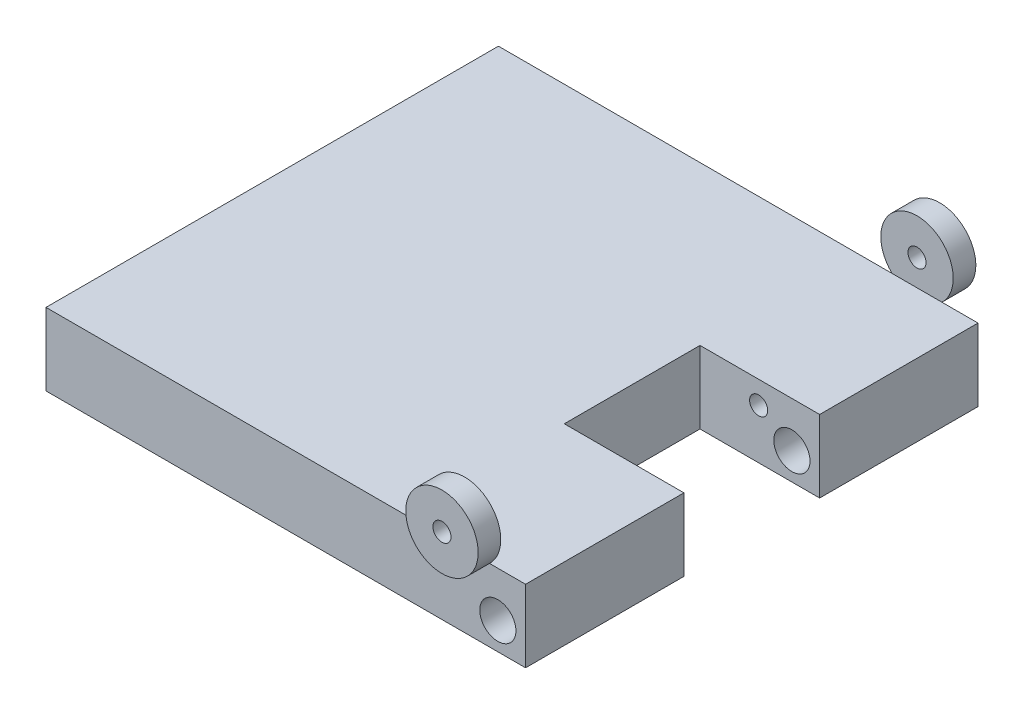
SolidWorks part; units mm, degrees
material "ABS"
ref_plane "Front Plane" through (0, 0, 0) normal (0, 0, 1) x (1, 0, 0)
ref_plane "Top Plane" through (0, 0, 0) normal (0, 1, 0) x (1, 0, 0)
ref_plane "Right Plane" through (0, 0, 0) normal (1, 0, 0) x (0, 0, -1)
sketch "Sketch1" plane through (0, 0, 0) normal (0, 0, 1) x (1, 0, 0)
  line L4 (0.9398, -1.27) -> (-66.3702, -1.27)
  line L5 (-66.3702, -1.27) -> (-66.3702, 8.89)
  line L6 (-66.3702, 8.89) -> (0.9398, 8.89)
  line L7 (0.9398, 8.89) -> (0.9398, -1.27)
  circle A6 centre (-2.9549, 2.54) radius 2.54
  point P3 (0, 0)
  dimension "D1" = 67.31
  dimension "D2" = 10.16
  dimension "D3" = 5.08
extrude "Boss-Extrude2" add sketch "Sketch1" along normal blind 63.5
sketch "Sketch2" plane through (0.9398, 0, 0) normal (1, 0, 0) x (0, 0, -1)
  line L0 (-31.75, 8.89) -> (-22.225, 8.89)
  line L1 (-63.5, 8.89) -> (0, 8.89) construction
  line L2 (-31.75, 8.89) -> (-41.275, 8.89)
  line L4 (-41.275, 8.89) -> (-41.275, -1.27)
  line L5 (-63.5, -1.27) -> (0, -1.27) construction
  line L6 (-41.275, -1.27) -> (-22.225, -1.27)
  line L7 (-22.225, -1.27) -> (-22.225, 8.89)
extrude "Cut-Extrude1" cut sketch "Sketch2" against normal blind 16.7894
sketch "Sketch3" plane through (0, 0, 41.275) normal (0, 0, -1) x (-1, 0, 0)
  circle A0 centre (7.62, 5.715) radius 1.27
extrude "Cut-Extrude2" cut sketch "Sketch3" against normal blind 12.7
sketch "Sketch4" plane through (0, 0, 22.225) normal (0, 0, 1) x (1, 0, 0)
  circle A0 centre (-7.62, 5.715) radius 1.27
extrude "Cut-Extrude3" cut sketch "Sketch4" against normal blind 12.7
sketch "Sketch5" plane through (0, 0, 63.5) normal (0, 0, 1) x (1, 0, 0)
  circle A0 centre (-7.62, 12.573) radius 1.27
  circle A1 centre (-7.62, 12.573) radius 5.08
extrude "Boss-Extrude3" add sketch "Sketch5" along normal blind 3.175
sketch "Sketch6" plane through (0, 0, 0) normal (0, 0, -1) x (-1, 0, 0)
  line L0 (7.62, 5.715) -> (7.62, 12.573) construction
  circle A0 centre (7.62, 12.573) radius 1.27
  circle A1 centre (7.62, 12.573) radius 5.08
extrude "Boss-Extrude4" add sketch "Sketch6" along normal blind 3.175
